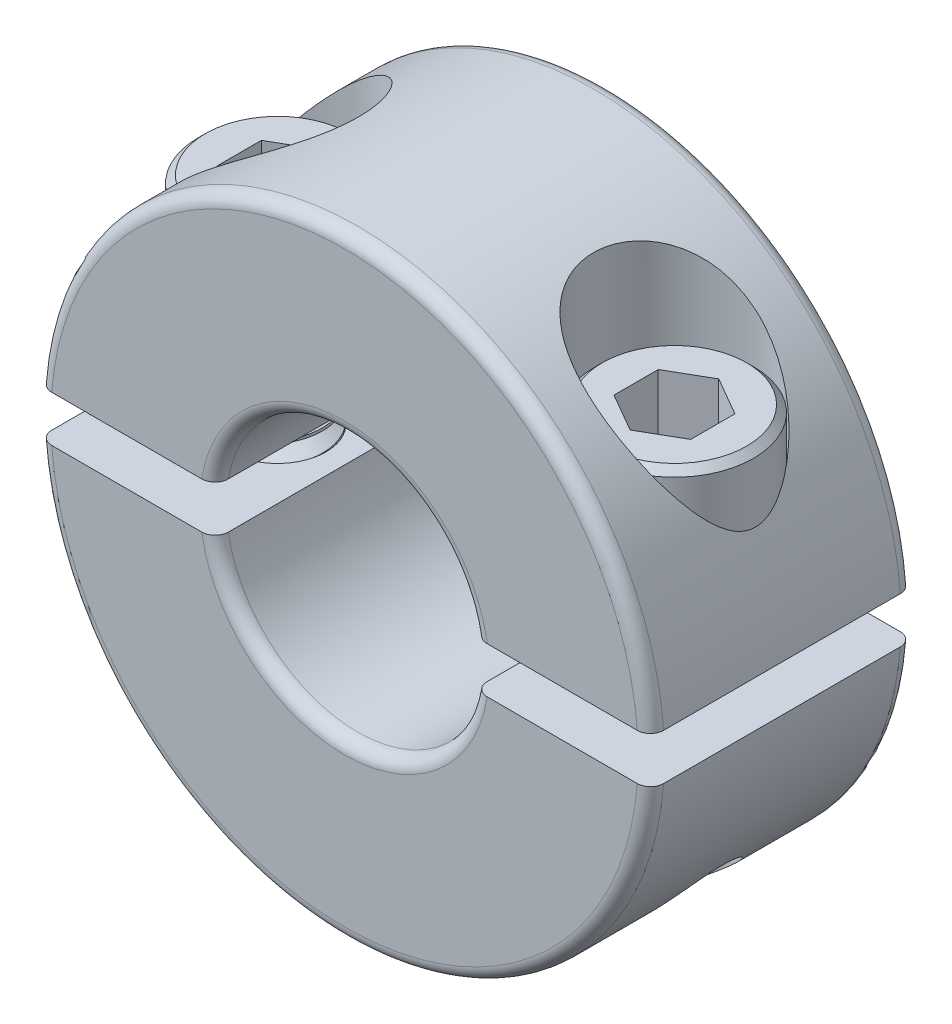
SolidWorks part; units mm, degrees
ref_plane "Front Plane" through (0, 0, 0) normal (0, 0, 1) x (1, 0, 0)
ref_plane "Top Plane" through (0, 0, 0) normal (0, 1, 0) x (1, 0, 0)
ref_plane "Right Plane" through (0, 0, 0) normal (1, 0, 0) x (0, 0, -1)
sketch "Sketch1" plane through (0, 0, 0) normal (0, 0, 1) x (1, 0, 0)
  line L0 (-11.1125, 0) -> (-4.7625, 0) construction
  line L1 (-11.0812, 0.8334) -> (-4.689, 0.8334)
  line L2 (-11.0812, -0.8334) -> (-4.689, -0.8334)
  line L3 (4.689, 0.8334) -> (11.0812, 0.8334)
  line L4 (4.689, -0.8334) -> (11.0812, -0.8334)
  line L5 (0, 0) -> (0, 11.1125) construction
  line L6 (-7.1882, 0.8334) -> (-7.1882, -0.8334) construction
  circle A0 centre (0, 0) radius 11.1125 construction
  circle A1 centre (0, 0) radius 4.7625 construction
  arc A4 (-4.689, -0.8334) -> (4.689, -0.8334) centre (0, 0) ccw
  arc A5 (-11.0812, -0.8334) -> (11.0812, -0.8334) centre (0, 0) ccw
  arc A6 (4.689, 0.8334) -> (-4.689, 0.8334) centre (0, 0) ccw
  arc A7 (11.0812, 0.8334) -> (-11.0812, 0.8334) centre (0, 0) ccw
  point P4 (11.1125, 0)
  point P14 (-11.1125, 0)
  point P18 (-7.1882, 6.9675)
  point P19 (-4.7625, 0)
  point P21 (4.7625, 0)
  point P22 (-10.0584, 6.9675)
  point P23 (-10.0584, 3.4623)
  point P24 (-8.9408, -6.0627)
  point P26 (-8.9408, -5.2689)
  point P29 (-8.5773, 6.9675)
  dimension "OD" = 22.225
  dimension "Separation" = 1.6669
  dimension "Screw Center to Center" = 14.3764
  dimension "Screw Size" = 3.5052
  dimension "Screw Head Height" = 3.5052
  dimension "Screw Head OD" = 5.7404
  dimension "Screw Thread Length" = 9.525
  dimension "D1" = 2.6289
  dimension "Hex" = 2.7781
  dimension "Pitch" = 0.7937
sketch "Sketch9" plane through (0, 0, 0) normal (1, 0, 0) x (0, 0, -1)
  line L0 (-4.7625, 0) -> (4.7625, 0) construction
  dimension "Width" = 9.525
sketch "Sketch10" plane through (0, 0, 0) normal (0, 0, 1) x (1, 0, 0)
  line L2 (-4.689, -0.8334) -> (-11.0812, -0.8334)
  line L3 (11.0812, -0.8334) -> (4.689, -0.8334)
  line L4 (-4.689, -0.8334) -> (-11.0812, -0.8334)
  line L5 (11.0812, -0.8334) -> (4.689, -0.8334)
  line L6 (-11.0812, 0.8334) -> (-4.689, 0.8334)
  line L7 (4.689, 0.8334) -> (11.0812, 0.8334)
  line L8 (-11.0812, 0.8334) -> (-4.689, 0.8334)
  line L9 (4.689, 0.8334) -> (11.0812, 0.8334)
  arc A2 (-4.689, -0.8334) -> (4.689, -0.8334) centre (0, 0) ccw
  arc A3 (-11.0812, -0.8334) -> (11.0812, -0.8334) centre (0, 0) ccw
  arc A4 (-4.689, -0.8334) -> (4.689, -0.8334) centre (0, 0) ccw
  arc A5 (-11.0812, -0.8334) -> (11.0812, -0.8334) centre (0, 0) ccw
  arc A6 (4.689, 0.8334) -> (-4.689, 0.8334) centre (0, 0) ccw
  arc A7 (11.0812, 0.8334) -> (-11.0812, 0.8334) centre (0, 0) ccw
  arc A8 (4.689, 0.8334) -> (-4.689, 0.8334) centre (0, 0) ccw
  arc A9 (11.0812, 0.8334) -> (-11.0812, 0.8334) centre (0, 0) ccw
  dimension "D1" = 0
  dimension "D2" = 0
extrude "Boss-Extrude1" add sketch "Sketch10" along normal mid plane 9.525 separate body
fillet "Fillet1" radius 0.4763 4 edges at (0, 4.7625, -4.7625) (0, 11.1125, -4.7625) (0, 4.7625, 4.7625) (0, 11.1125, 4.7625)
fillet "Fillet2" radius 0.4762 4 edges at (0, -11.1125, -4.7625) (0, -11.1125, 4.7625) (0, -4.7625, -4.7625) (0, -4.7625, 4.7625)
sketch "Sketch2" plane through (0, 0, 0) normal (0, 1, 0) x (1, 0, 0)
  line L0 (0, 4.7625) -> (0, -4.7625) construction
  line L1 (10.6035, 4.7625) -> (-10.6035, 4.7625) construction
  line L2 (-10.6035, -4.7625) -> (10.6035, -4.7625) construction
  line L3 (0, 0) -> (-4.7625, 0) construction
  line L4 (-4.7625, 0) -> (-11.1125, 0) construction
  line L7 (-7.9375, 4.7625) -> (-7.9375, -4.7625) construction
  line L8 (-8.128, 4.7625) -> (-7.747, 4.7625)
  line L10 (-11.1125, 0) -> (-4.7625, 0) construction
  arc A0 (-8.128, 4.7625) -> (-7.747, 4.7625) centre (-7.9375, 4.7625) ccw
  point P16 (-7.9375, 0)
  dimension "D2" = 0.1905
revolve "Cut-Revolve1" cut sketch "Sketch2" angle 360 about L0
sketch "Sketch3" plane through (0, 0, 0) normal (0, 0, 1) x (1, 0, 0)
  line L0 (-7.1882, 11.1125) -> (-4.2545, 11.1125)
  line L1 (-4.2545, 11.1125) -> (-4.2545, 3.4623)
  line L2 (-4.2545, 3.4623) -> (-5.4356, 3.4623)
  line L3 (-5.4356, 3.4623) -> (-5.4356, -11.1125)
  line L4 (-5.4356, -11.1125) -> (-7.1882, -11.1125)
  line L5 (-7.1882, -11.1125) -> (-7.1882, 11.1125)
  line L7 (-7.1882, 11.1125) -> (-7.1882, 14.0462) construction
  line L8 (-4.2545, 11.1125) -> (0, 11.1125) construction
  line L9 (0, -11.1125) -> (-5.4356, -11.1125) construction
  line L10 (-11.1125, 0) -> (-4.7625, 0) construction
  line L12 (0, 0) -> (0, -11.1125) construction
  line L14 (-7.1882, 0.8334) -> (-7.1882, -0.8334) construction
  circle A0 centre (0, 0) radius 11.1125 construction
  circle A2 centre (0, 0) radius 4.7625 construction
  arc A4 (-11.0812, -0.8334) -> (11.0812, -0.8334) centre (0, 0) ccw construction
  dimension "D1" = 5.8674
revolve "Cut-Revolve2" cut sketch "Sketch3" angle 360 about L5
mirror "Mirror1" about plane through (0, 0, 0) normal (1, 0, 0) of "Cut-Revolve2"
sketch "Sketch4" plane through (0, 0, 0) normal (0, 0, 1) x (1, 0, 0)
  line L0 (-7.1882, 6.9675) -> (-4.318, 6.9675)
  line L2 (-4.318, 6.9675) -> (-4.318, 3.4623)
  line L3 (-4.318, 3.4623) -> (-5.4356, 3.4623)
  line L4 (-5.4356, 3.4623) -> (-5.4356, -6.0627)
  line L5 (-5.4356, 3.4623) -> (-5.4356, -11.1125) construction
  line L6 (-5.4356, -6.0627) -> (-7.1882, -6.0627)
  line L7 (-7.1882, -11.1125) -> (-7.1882, 11.1125) construction
  line L8 (-7.1882, -6.0627) -> (-7.1882, 6.9675)
  line L9 (-5.4356, -6.0627) -> (-8.9408, -6.0627) construction
  line L10 (-7.1882, 6.9675) -> (-7.1882, 9.8377) construction
  dimension "Screw Lg" = 9.525
  dimension "Head Dia" = 5.7404
revolve "Revolve1" add sketch "Sketch4" angle 360 about L8
sketch "Sketch5" plane through (0, 6.9675, 0) normal (0, 1, 0) x (-1, 0, 0)
  line L1 (7.1882, 1.604) -> (5.7991, 0.802)
  line L2 (5.7991, 0.802) -> (5.7991, -0.802)
  line L3 (5.7991, -0.802) -> (7.1882, -1.604)
  line L4 (7.1882, -1.604) -> (8.5773, -0.802)
  line L5 (8.5773, -0.802) -> (8.5773, 0.802)
  line L6 (8.5773, 0.802) -> (7.1882, 1.604)
  circle A0 centre (7.1882, 0) radius 1.3891 construction
  dimension "D1" = 2.7781
extrude "Cut-Extrude2" cut sketch "Sketch5" against normal blind 2.6289
chamfer "Chamfer3" distance 0.5953 angle 45 1 edges at (-7.1882, -6.0627, -1.7526)
chamfer "Chamfer1" distance 0.254 angle 45 1 edges at (-7.1882, 6.9675, -2.8702)
sketch "Sketch6" plane through (0, -6.0627, 0) normal (0, -1, 0) x (1, 0, 0)
  circle A0 centre (-7.1882, 0) radius 1.7526 construction
  circle A1 centre (-7.1882, 0) radius 1.7526
  point P3 (-8.9408, 0)
pattern_linear "LPattern2" count 2 spacing 14.3764 along (1, 0, 0) of bodies 182
curve "Helix/Spiral1" pitch 0.7937 height 9.525 turns 12 parameters "Height"=9.525, "Pitch"=0.7937
sketch "Sketch7" plane through (0, 0, 0) normal (0, 0, 1) x (1, 0, 0)
  line L0 (-9.0267, -6.0131) -> (-9.0267, -6.8068) construction
  line L1 (-9.0267, -6.8068) -> (-8.3393, -6.4099) construction
  line L2 (-8.3393, -6.4099) -> (-9.0267, -6.0131) construction
  line L3 (-9.0267, -6.4099) -> (-8.9408, -6.4099) construction
  line L4 (-8.3393, -6.4099) -> (-8.4252, -6.4099) construction
  line L5 (-8.4252, -6.3603) -> (-8.4252, -6.4595)
  line L6 (-8.9408, -6.7572) -> (-8.9408, -6.0627) construction
  line L7 (-8.4252, -6.3603) -> (-8.9838, -6.0379)
  line L8 (-8.9838, -6.0379) -> (-8.9838, -6.782)
  line L9 (-8.9838, -6.782) -> (-8.4252, -6.4595)
  point P10 (-8.9838, -6.4099)
  dimension "D1" = 0.7937
  dimension "D2" = 0.0992
sweep "Cut-Sweep1" cut profiles "Sketch7" path "Helix/Spiral1"
pattern_linear "LPattern1" count 2 spacing 14.3764 along (-1, 0, 0)
delete or keep bodies "Body-Delete/Keep 1" type delete bodies bodies 183
equation "\"D1@Sketch3\"=\"Screw Head OD@Sketch1\"+.005"
equation "\"D1@Cut-Extrude2\" = \"Screw Head Height@Sketch1\" * .750"
equation "\"Height@Helix/Spiral1\" = \"Screw Thread Length@Sketch1\""
equation "\"D1@Sketch7\" = \"Pitch@Sketch1\""
equation "\"D2@Sketch7\" = \"D1@Sketch7\"/8"
equation "\"D3@LPattern1\"=\"Screw Center to Center@Sketch1\""
equation "\"D1@Sketch1\"=\"Screw Size@Sketch1\"*0.75"
equation "\"D1@Boss-Extrude1\" = \"Width@Sketch9\""
equation "\"D1@Fillet1\" = \"Width@Sketch9\" * .05"
equation "\"D1@Fillet2\"=\"D1@Fillet1\""
equation "\"Screw Dia@Sketch3\"=\"Screw Size@Sketch1\""
equation "\"Head Ht@Sketch4\"=\"Screw Head Height@Sketch1\""
equation "\"Screw Lg@Sketch4\"=\"Screw Thread Length@Sketch1\""
equation "\"Head Dia@Sketch4\"=\"Screw Head OD@Sketch1\""
equation "\"D1@Sketch5\" = \"Hex@Sketch1\""
equation "\"D1@Chamfer3\" = \"Pitch@Sketch1\" * 0.75"
equation "\"D3@LPattern2\" = \"Screw Center to Center@Sketch1\""
equation "\"Pitch@Helix/Spiral1\" = \"Pitch@Sketch1\""
